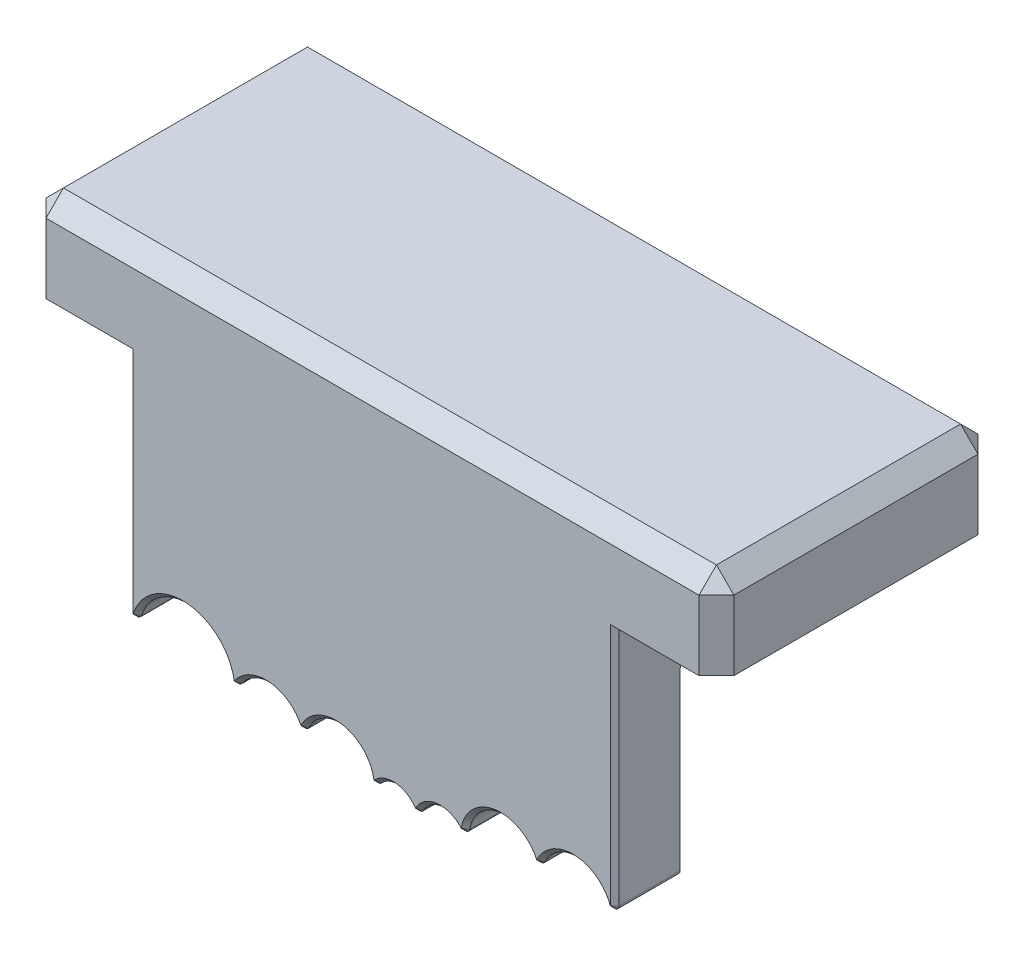
SolidWorks part; units mm, degrees
ref_plane "Front Plane" through (0, 0, 0) normal (0, 0, 1) x (1, 0, 0)
ref_plane "Top Plane" through (0, 0, 0) normal (0, 1, 0) x (1, 0, 0)
ref_plane "Right Plane" through (0, 0, 0) normal (1, 0, 0) x (0, 0, -1)
sketch "Sketch1" plane through (0, 0, 0) normal (0, 1, 0) x (1, 0, 0)
  point P0 (0, 0)
  point P1 (38.8013, -7.1245)
  line B0 (28.37, 45.6802) -> (28.37, 0) construction
  line B1 (28.37, 0) -> (39.45, 0) construction
  line B2 (39.45, 0) -> (39.45, 39.05) construction
  line B3 (39.45, 39.05) -> (36.7, 40.8) construction
  line B4 (36.7, 40.8) -> (36.7, 59.75) construction
  line B5 (36.7, 59.75) -> (32.77, 59.75) construction
  line B6 (32.77, 59.75) -> (32.77, 45.6802) construction
  line B7 (32.77, 45.6802) -> (28.37, 45.6802) construction
  line B8 (-28.37, 0) -> (-28.37, 45.6802) construction
  line B9 (-28.37, 45.6802) -> (-32.77, 45.6802) construction
  line B10 (-32.77, 45.6802) -> (-32.77, 59.75) construction
  line B11 (-32.77, 59.75) -> (-36.7, 59.75) construction
  line B12 (-36.7, 59.75) -> (-36.7, 40.8) construction
  line B13 (-36.7, 40.8) -> (-39.45, 39.05) construction
  line B14 (-39.45, 39.05) -> (-39.45, 0) construction
  line B15 (-39.45, 0) -> (-28.37, 0) construction
  line B16 (28.37, 0) -> (-28.37, 0) construction
  circle B17 centre (34.45, 9.5) radius 2.95 construction
  circle B18 centre (34.45, 25.5) radius 2.95 construction
  circle B19 centre (-34.45, 9.5) radius 2.95 construction
  circle B20 centre (-34.45, 25.5) radius 2.95 construction
sketch_block_instance "Block1-1"
sketch_block "Block1"
sketch "Sketch2" plane through (0, 0, 0) normal (0, 0, 1) x (1, 0, 0)
  point P0 (-28.4528, 0)
  line B0 (-39.5328, 0) -> (-39.5328, -39.5) construction
  line B1 (-39.5328, -39.5) -> (-28.4528, -39.5) construction
  line B2 (-28.4528, -39.5) -> (-28.4528, 0) construction
  line B3 (-28.4528, 0) -> (-39.5328, 0) construction
  line B4 (39.3672, -39.5) -> (39.3672, 0) construction
  line B5 (39.3672, 0) -> (28.2872, 0) construction
  line B6 (28.2872, 0) -> (28.2872, -39.5) construction
  line B7 (28.2872, -39.5) -> (39.3672, -39.5) construction
  circle B8 centre (-34.5328, -11.75) radius 2.95 construction
  circle B9 centre (34.3672, -11.75) radius 2.95 construction
  circle B10 centre (-34.5328, -27.75) radius 2.95 construction
  circle B11 centre (34.3672, -27.75) radius 2.95 construction
sketch_block_instance "Block2-1"
sketch_block "Block2"
ref_plane "Plane1" through (0, -39.5, 0) normal (0, 1, 0) x (1, 0, 0)
sketch "Sketch3" plane through (0, 0, 0) normal (0, 1, 0) x (1, 0, 0)
  line L0 (-39.45, 0) -> (-39.45, 32)
  line L1 (-39.45, 39.05) -> (-39.45, 0) construction
  line L2 (-39.45, 32) -> (39.45, 32)
  line L3 (39.45, 0) -> (39.45, 39.05) construction
  line L4 (39.45, 32) -> (39.45, 0)
  line L5 (39.45, 0) -> (-39.45, 0)
  circle A0 centre (-34.45, 9.5) radius 2.375
  circle A1 centre (34.45, 9.5) radius 2.375
  circle A2 centre (-34.45, 25.5) radius 2.375
  circle A3 centre (34.45, 25.5) radius 2.375
  dimension "D2" = 4.75
  dimension "D1" = 32
extrude "Boss-Extrude1" add sketch "Sketch3" along normal blind 10 contours L2 L4 L5 L0
extrude "Cut-Extrude1" cut sketch "Sketch3<4>" along normal blind 8 contours A0 | A1 | A2 | A3
sketch "Sketch3<4>" plane through (0, 0, 0) normal (0, 1, 0) x (1, 0, 0) same geometry as "Sketch3"
sketch "Sketch4" plane through (0, 0, 0) normal (0, 0, 1) x (1, 0, 0)
  line L2 (-27.9528, -39.5) -> (-27.9528, 0)
  line L3 (-27.9528, -33.5) -> (-27.9528, 0)
  line L4 (-27.9528, 0) -> (27.7872, 0)
  line L5 (27.7872, 0) -> (27.7872, -39.5)
  line L6 (27.7872, 0) -> (27.7872, -33.5)
  line L7 (-27.9528, -33.5) -> (27.7872, -33.5)
  dimension "D3" = 33.5
  dimension "D1" = 0.5
  dimension "D2" = 0.5
extrude "Boss-Extrude2" add sketch "Sketch4" against normal blind 8
sketch "Sketch6" plane through (0, 0, 0) normal (0, 0, 1) x (1, 0, 0)
  line L0 (-27.1328, -28.125) -> (-16.3828, -28.125) construction
  line L1 (-16.0328, -29.675) -> (-8.3828, -29.675) construction
  line L2 (-8.0328, -29.675) -> (-0.3828, -29.675) construction
  line L3 (-0.0328, -31.075) -> (4.8172, -31.075) construction
  line L4 (5.1672, -30.9) -> (10.3672, -30.9) construction
  line L5 (10.7172, -29.525) -> (18.6672, -29.525) construction
  line L6 (19.0172, -29.525) -> (26.9672, -29.525) construction
  line L7 (-27.9528, -33.5) -> (27.7872, -33.5) construction
  line L10 (-27.9528, -33.5) -> (27.7872, -33.5)
  line L11 (-27.1328, -28.125) -> (-27.9528, -28.125) construction
  line L12 (-27.9528, 0) -> (-27.9528, -33.5) construction
  line L13 (26.9672, -29.525) -> (27.7872, -29.525) construction
  line L14 (27.7872, -33.5) -> (27.7872, 0) construction
  line L23 (-27.9528, -33.5) -> (-27.9528, -26.3173)
  line L24 (27.7872, -27.9491) -> (27.7872, -33.5)
  circle A0 centre (-21.7578, -28.125) radius 5.375 construction
  circle A1 centre (-12.2078, -29.675) radius 3.825 construction
  circle A2 centre (-4.2078, -29.675) radius 3.825 construction
  circle A3 centre (2.3922, -31.075) radius 2.425 construction
  circle A4 centre (7.7672, -30.9) radius 2.6 construction
  circle A5 centre (14.6922, -29.525) radius 3.975 construction
  circle A6 centre (22.9922, -29.525) radius 3.975 construction
  arc A7 (-16.3524, -27.2544) -> (-26.9762, -26.4686) centre (-21.7578, -28.125) ccw
  arc A8 (-8.6597, -27.9966) -> (-15.4462, -27.4574) centre (-12.2078, -29.675) ccw
  arc A9 (-0.3255, -29.0973) -> (-7.7558, -27.9966) centre (-4.2078, -29.675) ccw
  arc A10 (4.5085, -29.6976) -> (0.5365, -29.3627) centre (2.3922, -31.075) ccw
  arc A11 (9.7997, -29.1226) -> (5.3712, -29.6554) centre (7.7672, -30.9) ccw
  arc A12 (18.3887, -27.8098) -> (10.6697, -28.8734) centre (14.6922, -29.525) ccw
  arc A13 (26.8178, -28.1213) -> (19.2958, -27.8098) centre (22.9922, -29.525) ccw
  circle A14 centre (-21.7578, -28.125) radius 5.475 construction
  circle A15 centre (-12.2078, -29.675) radius 3.925 construction
  circle A16 centre (-4.2078, -29.675) radius 3.925 construction
  circle A17 centre (2.3922, -31.075) radius 2.525 construction
  circle A18 centre (7.7672, -30.9) radius 2.7 construction
  circle A19 centre (14.6922, -29.525) radius 4.075 construction
  circle A20 centre (22.9922, -29.525) radius 4.075 construction
  arc A21 (-16.3524, -27.2544) -> (-15.4462, -27.4574) centre (-15.8588, -27.1749) ccw
  arc A22 (-8.6597, -27.9966) -> (-7.7558, -27.9966) centre (-8.2078, -27.7827) ccw
  arc A23 (-0.3255, -29.0973) -> (0.5365, -29.3627) centre (0.169, -29.0237) ccw
  arc A24 (4.5085, -29.6976) -> (5.3712, -29.6554) centre (4.9275, -29.4249) ccw
  arc A25 (9.7997, -29.1226) -> (10.6697, -28.8734) centre (10.1761, -28.7935) ccw
  arc A26 (18.3887, -27.8098) -> (19.2958, -27.8098) centre (18.8422, -27.5994) ccw
  arc A27 (26.8178, -28.1213) -> (27.7872, -27.9491) centre (27.2872, -27.9491) ccw
  arc A28 (-27.9528, -26.3173) -> (-26.9762, -26.4686) centre (-27.4528, -26.3173) ccw
  dimension "D1" = 7.95
  dimension "D2" = 7.95
  dimension "D3" = 5.2
  dimension "D4" = 4.85
  dimension "D5" = 7.65
  dimension "D6" = 7.65
  dimension "D7" = 10.75
  dimension "D15" = 1
  dimension "D9" = 0.35
  dimension "D10" = 0.35
  dimension "D12" = 0.35
  dimension "D13" = 0.35
  dimension "D14" = 0.35
  dimension "D8" = 0.35
  dimension "D11" = 0.1
extrude "Cut-Extrude2" cut sketch "Sketch6" against normal up to next
fillet "Fillet1" radius 8 1 edges at (-0.0828, 0, -8)
chamfer "Chamfer1" distance 2 angle 45 8 edges at (0, 10, -32) (39.45, 5, -32) (39.45, 10, -16) (39.45, 5, 0) (0, 10, 0) (-39.45, 5, -32) (-39.45, 10, -16) (-39.45, 5, 0)
chamfer "Chamfer2" distance 0.5 angle 45 36 edges at (27.7872, -2.3431, -10.3431) (27.7872, -17.9745, -8) (27.3747, -28.4413, -8) (23.1608, -25.4535, -8) (18.8422, -28.0994, -8) (14.136, -25.4881, -8) (10.3138, -29.2742, -8) (7.4448, -28.2193, -8) (4.952, -29.9243, -8) (2.6044, -28.5589, -8) (0.0219, -29.5015, -8) (-3.6326, -25.7924, -8) (-8.2078, -28.2827, -8) (-11.8969, -25.7623, -8) (-15.9681, -27.6628, -8) (-21.3539, -22.6649, -8) (-27.9528, -2.3431, -10.3431) (-27.5293, -26.8115, -8) (-27.9528, -17.1587, -8) (27.7872, -13.9745, 0) (27.3747, -28.4413, 0) (23.1608, -25.4535, 0) (18.8422, -28.0994, 0) (14.136, -25.4881, 0) (10.3138, -29.2742, 0) (7.4448, -28.2193, 0) (4.952, -29.9243, 0) (2.6044, -28.5589, 0) (0.0219, -29.5015, 0) (-3.6326, -25.7924, 0) (-8.2078, -28.2827, 0) (-11.8969, -25.7623, 0) (-15.9681, -27.6628, 0) (-21.3539, -22.6649, 0) (-27.5293, -26.8115, 0) (-27.9528, -13.1587, 0)
equation "\"D14@Sketch6\"=\"D9@Sketch6\""
equation "\"D10@Sketch6\"=\"D9@Sketch6\""
equation "\"D13@Sketch6\"=\"D9@Sketch6\""
equation "\"D12@Sketch6\"=\"D9@Sketch6\""
equation "\"D8@Sketch6\"=\"D9@Sketch6\""
